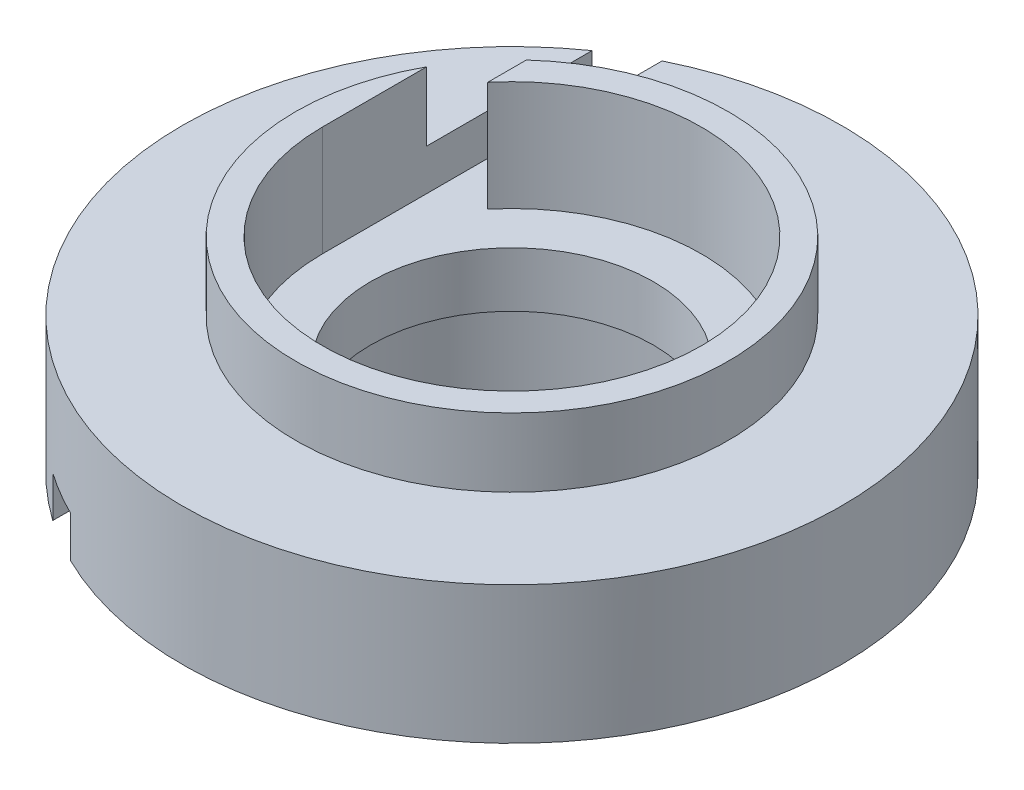
SolidWorks part; units mm, degrees
other "Markup1"
sketch "Sketch14" plane through (31.75, -16.51, 39.3443) normal (0.2842, -0.9484, 0.1408) x (0.2076, -0.0825, -0.9747)
ref_plane "Front Plane" through (0, 0, 0) normal (0, 0, 1) x (1, 0, 0)
ref_plane "Top Plane" through (0, 0, 0) normal (0, 1, 0) x (1, 0, 0)
ref_plane "Right Plane" through (0, 0, 0) normal (1, 0, 0) x (0, 0, -1)
sketch "Sketch1" plane through (0, 0, 0) normal (0, 1, 0) x (1, 0, 0)
  circle A0 centre (0, 0) radius 30.48
  circle A1 centre (0, 0) radius 13.081
  dimension "D1" = 60.96
  dimension "D2" = 26.162
extrude "Boss-Extrude1" add sketch "Sketch1" along normal mid plane 25.4
sketch "Sketch2" plane through (0, 12.7, 0) normal (0, 1, 0) x (1, 0, 0)
  line L0 (-17.526, 0) -> (-17.526, 24.9373)
  line L1 (-13.462, 11.2221) -> (-13.462, 27.346)
  arc A0 (-17.526, 0) -> (-13.462, 11.2221) centre (0, 0) ccw
  circle A1 centre (0, 0) radius 30.48 construction
  arc A2 (-13.462, 27.346) -> (-17.526, 24.9373) centre (0, 0) ccw
  dimension "D1" = 4.064
  dimension "D2" = 17.526
extrude "Cut-Extrude1" cut sketch "Sketch2" against normal blind 10.16
sketch "Sketch13" plane through (0, 12.7, 0) normal (0, 1, 0) x (1, 0, 0)
  circle A1 centre (0, 0) radius 20
  circle A2 centre (0, 0) radius 30.48
  arc A3 (-17.526, 24.9373) -> (-13.462, 27.346) centre (0, 0) ccw construction
  dimension "D1" = 40
extrude "Cut-Extrude2" cut sketch "Sketch13" against normal blind 6.35
sketch "Sketch5" plane through (0, 0, 0) normal (0, 1, 0) x (1, 0, 0)
  line L0 (0, -39.3443) -> (0, 40.2571) construction
  line L1 (0, -22.352) -> (0, 22.352) construction
ref_axis "Axis1" through (-0.5553, 0, 0) along (-1, 0, 0)
sketch "Sketch9" plane through (0, 0, 0) normal (0, 0, 1) x (1, 0, 0)
  line L0 (0, -22.352) -> (0, 22.352) construction
  line L1 (-20.066, 3.81) -> (-14.478, 3.81)
  line L2 (-20.066, 3.81) -> (-20.066, 0)
  line L3 (-20.066, 0) -> (-14.478, 0)
  line L4 (-14.478, 3.81) -> (-14.478, 0)
  point P5 (-14.478, 1.905)
  dimension "D1" = 3.81
  dimension "D2" = 14.478
sketch "Sketch12" plane through (0, 2.54, 0) normal (0, 1, 0) x (1, 0, 0)
  circle A0 centre (0, 0) radius 13.081
  circle A1 centre (0, 0) radius 13.081 construction
curve "Helix/Spiral2" pitch 3.302 height 2.9619 turns 0.897
pattern_circular "CirPattern1" count 2 every 180 about axis through (-0.5553, 0, 0) along (-1, 0, 0) of "Cut-Extrude2", "Cut-Extrude1"
